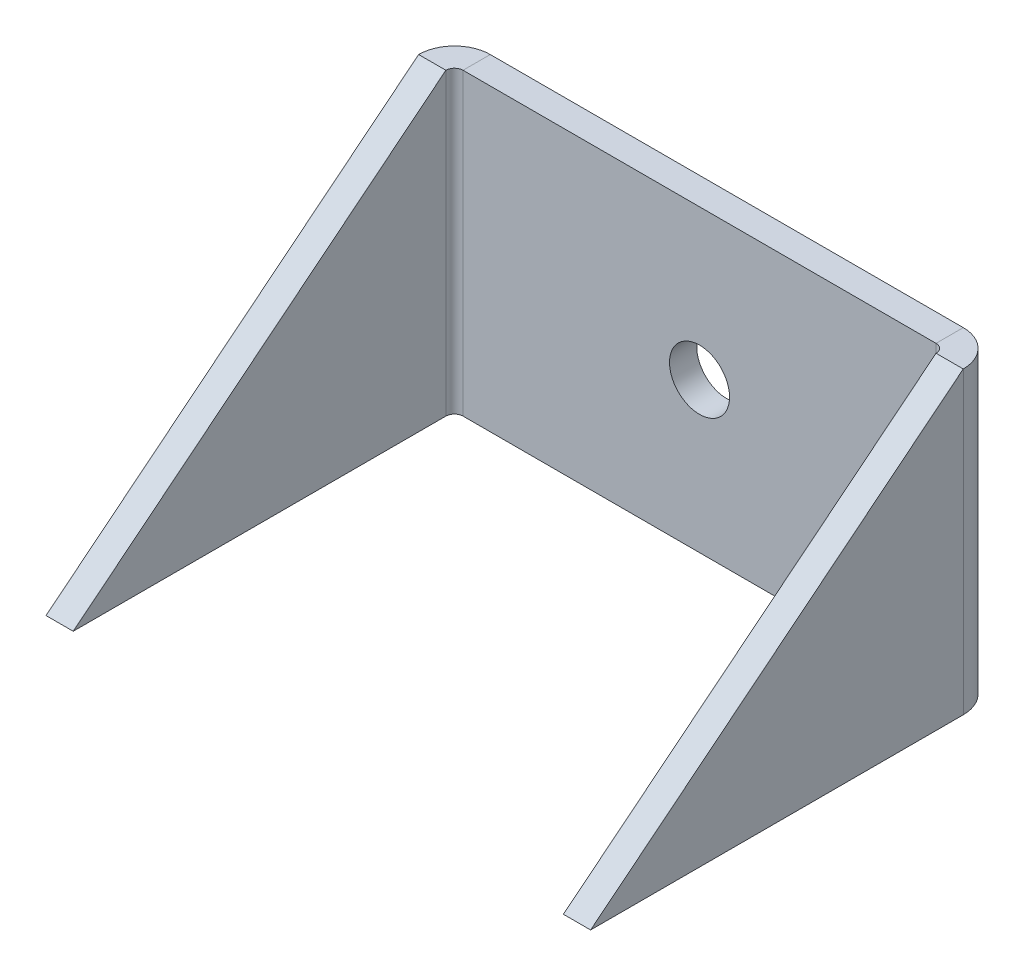
SolidWorks part; units mm, degrees
note: The reader was unsure of these and kept them because the rebuilt part matched: flange length of "Edge-Flange1".
material "6061-T6 (SS)"
ref_plane "X-Y Datum" through (0, 0, 0) normal (0, 0, 1) x (1, 0, 0)
ref_plane "X-Z Datum" through (0, 0, 0) normal (0, 1, 0) x (1, 0, 0)
ref_plane "Y-Z Datum" through (0, 0, 0) normal (1, 0, 0) x (0, 0, -1)
sketch "Sketch2" plane through (0, 0, 0) normal (0, 0, 1) x (1, 0, 0)
  line L1 (-28.575, 17.4625) -> (28.575, 17.4625)
  line L2 (-28.575, 17.4625) -> (-28.575, -17.4625)
  line L3 (-28.575, -17.4625) -> (28.575, -17.4625)
  line L4 (28.575, 17.4625) -> (28.575, -17.4625)
  line L5 (-28.575, 17.4625) -> (28.575, -17.4625) construction
  line L6 (-28.575, -17.4625) -> (28.575, 17.4625) construction
  circle A0 centre (0, 0) radius 3 construction
  point P0 (0, 0)
  dimension "D3" = 6
  dimension "D1" = 34.925
  dimension "D2" = 57.15
base flange "Base-Flange1" sketch "Sketch2" thickness 3.175 reverse thickness direction yes parameters "D1"=1
edge flange "Edge-Flange1" sketch "Sketch9" flange angle 90 flange length 47.625 flange position material outside bend radius 1 thickness 3.175 relief rectangular parameters "D6"=10
sketch "Sketch9" plane through (28.575, 0, 3.175) normal (1, 0, 0) x (0, 1, 0)
  line L2 (-17.4625, 0) -> (-17.4625, 44.45)
  line L3 (-17.4625, 44.45) -> (17.4625, 44.45)
  line L4 (17.4625, 44.45) -> (17.4625, 0)
  line L7 (-17.4625, 0) -> (17.4625, 0) construction
  line L8 (-17.4625, 0) -> (17.4625, 0)
bend "EdgeBend1" bend radius 1 bend angle 90 parameters "D5"=1
sketch "Sketch10" plane through (31.75, 0, 0) normal (1, 0, 0) x (0, 0, -1)
  line L0 (-4.175, 17.4625) -> (-47.625, -17.4625)
  line L1 (-47.625, 17.4625) -> (-47.625, -17.4625) construction
  line L3 (-47.625, -17.4625) -> (-4.175, -17.4625) construction
  line L7 (-4.175, -17.4625) -> (-4.175, 17.4625)
  line L8 (-4.175, 17.4625) -> (-47.625, 17.4625)
  line L9 (-47.625, 17.4625) -> (-47.625, -17.4625)
  line L10 (-47.625, -17.4625) -> (-4.175, -17.4625)
  line L12 (-4.175, 17.4625) -> (-47.625, 17.4625)
  line L13 (-47.625, 17.4625) -> (-47.625, -17.4625)
  dimension "D1" = 0
extrude "Cut-Extrude1" cut sketch "Sketch10" against normal blind 3.175 normal cut yes
mirror "Mirror1" about plane through (0, 0, 0) normal (1, 0, 0) of "Cut-Extrude1", "Edge-Flange1"
bend "MirrorBend1" bend radius 1 bend angle 90 parameters "D5"=2
sketch "Sketch11" [suppressed] plane through (32.75, 0, 0) normal (1, 0, 0) x (0, 0, -1)
  line L0 (-4.175, -15.875) -> (-44.45, 15.875)
extrude "Cut-Extrude2" [suppressed] cut sketch "Sketch11" against normal blind 3.175 and the other way through all
hole_wizard "M6 Clearance Hole1" positions "Sketch13" profile "Sketch14" hole size "M6" standard "ANSI Metric" end condition through all
sketch "Sketch13" plane through (0, 0, 3.175) normal (0, 0, 1) x (1, 0, 0)
  point P0 (0, 0)
sketch "Sketch14" plane through (0, 0, 3.175) normal (1, 0, 0) x (0, -1, 0)
  line L0 (0, 0) -> (0, 3.175)
  line L1 (0, 3.175) -> (3.5, 3.175)
  line L2 (3.5, 3.175) -> (3.5, 0)
  line L5 (3.5, 0) -> (0, 0)
  line L11 (0, -6.35) -> (0, 107.95) construction
  dimension "Thru Hole Dia." = 7
  dimension "Thru Hole Depth" = 3.175
sketch "Bend-Lines1" [suppressed] plane through (0, 0, 0) normal (0, 1, 0) x (1, 0, 0)
sketch "Bounding-Box1" [suppressed] plane through (0, 0, 0) normal (0, 1, 0) x (1, 0, 0)
sheet metal parameters "Sheet-Metal1" thickness 3.175 parameters "D1"=1
flat pattern "Flat-Pattern1" [suppressed]
sketch "Bend-Lines2" plane through (0, 0, 0) normal (0, 1, 0) x (1, 0, 0)
sketch3d "Bounding-Box2" [suppressed]
  line L0 (-63.5, -15.875, 0) -> (63.5, -15.875, 0) construction
  line L1 (-63.5, 15.875, 0) -> (63.5, 15.875, 0) construction
  line L2 (-63.5, -15.875, 0) -> (-63.5, 15.875, 0) construction
  line L3 (63.5, -15.875, 0) -> (63.5, 15.875, 0) construction
sheet metal parameters "Sheet-Metal2" thickness 3.175 parameters "D1"=1
flat pattern "Flat-Pattern1"
sketch "Bend-Lines2" plane through (0, 0, 0) normal (0, 0, -1) x (-1, 0, 0)
  line L0 (-30.6072, 15.875) -> (-30.6072, -15.875) construction
  line L1 (-30.6072, 15.875) -> (-30.6072, -15.875) construction
sketch3d "Bounding-Box2" [suppressed]
  line L0 (28.575, -15.875, 0) -> (-72.9144, -15.875, 0) construction
  line L1 (28.575, 15.875, 0) -> (-72.9144, 15.875, 0) construction
  line L2 (28.575, -15.875, 0) -> (28.575, 15.875, 0) construction
  line L3 (-72.9144, -15.875, 0) -> (-72.9144, 15.875, 0) construction
bend of the flat pattern "Flatten-<EdgeBend1>1"
sheet metal parameters "Sheet-Metal5" thickness 3.175 parameters "D1"=1
flat pattern "Flat-Pattern1"
sketch "Bend-Lines2" plane through (0, 0, 0) normal (0, 0, -1) x (-1, 0, 0)
  line L0 (-29.6072, 15.875) -> (-29.6072, -15.875) construction
  line L1 (-29.6072, 15.875) -> (-29.6072, -15.875) construction
  line L2 (29.6072, -15.875) -> (29.6072, 15.875) construction
  line L3 (29.6072, -15.875) -> (29.6072, 15.875) construction
sketch3d "Bounding-Box2" [suppressed]
  line L0 (71.9144, -15.875, 0) -> (-71.9144, -15.875, 0) construction
  line L1 (71.9144, 15.875, 0) -> (-71.9144, 15.875, 0) construction
  line L2 (71.9144, -15.875, 0) -> (71.9144, 15.875, 0) construction
  line L3 (-71.9144, -15.875, 0) -> (-71.9144, 15.875, 0) construction
bend of the flat pattern "Flatten-<EdgeBend1>1"
bend of the flat pattern "Flatten-<MirrorBend1>1"
sheet metal parameters "Sheet-Metal7" thickness 3.175 parameters "D1"=1
flat pattern "Flat-Pattern1"
sketch "Bend-Lines2" plane through (0, 0, 0) normal (0, 0, -1) x (-1, 0, 0)
  line L0 (-30.6072, 15.875) -> (-30.6072, -15.875) construction
  line L1 (-30.6072, 15.875) -> (-30.6072, -15.875) construction
sketch3d "Bounding-Box2" [suppressed]
  line L0 (28.575, -15.875, 0) -> (-72.9144, -15.875, 0) construction
  line L1 (28.575, 15.875, 0) -> (-72.9144, 15.875, 0) construction
  line L2 (28.575, -15.875, 0) -> (28.575, 15.875, 0) construction
  line L3 (-72.9144, -15.875, 0) -> (-72.9144, 15.875, 0) construction
bend of the flat pattern "Flatten-<EdgeBend1>1"
sheet metal parameters "Sheet-Metal8" thickness 3.175 parameters "D1"=1
flat pattern "Flat-Pattern1"
sketch "Bend-Lines2" plane through (0, 0, 0) normal (0, 0, -1) x (-1, 0, 0)
  line L0 (-30.6072, 15.875) -> (-30.6072, -15.875) construction
  line L1 (-30.6072, 15.875) -> (-30.6072, -15.875) construction
sketch3d "Bounding-Box2" [suppressed]
  line L0 (28.575, -15.875, 0) -> (-72.9144, -15.875, 0) construction
  line L1 (28.575, 15.875, 0) -> (-72.9144, 15.875, 0) construction
  line L2 (28.575, -15.875, 0) -> (28.575, 15.875, 0) construction
  line L3 (-72.9144, -15.875, 0) -> (-72.9144, 15.875, 0) construction
bend of the flat pattern "Flatten-<EdgeBend1>1"
sheet metal parameters "Sheet-Metal9" thickness 3.175 parameters "D1"=1
flat pattern "Flat-Pattern1"
sketch "Bend-Lines2" plane through (0, 0, 0) normal (0, 0, -1) x (-1, 0, 0)
  line L0 (-29.6072, 17.4625) -> (-29.6072, -17.4625) construction
  line L1 (-29.6072, 17.4625) -> (-29.6072, -17.4625) construction
  line L2 (29.6072, -17.4625) -> (29.6072, 17.4625) construction
  line L3 (29.6072, -17.4625) -> (29.6072, 17.4625) construction
sketch3d "Bounding-Box2" [suppressed]
  line L0 (75.0894, -17.4625, 0) -> (-75.0894, -17.4625, 0) construction
  line L1 (75.0894, 17.4625, 0) -> (-75.0894, 17.4625, 0) construction
  line L2 (75.0894, -17.4625, 0) -> (75.0894, 17.4625, 0) construction
  line L3 (-75.0894, -17.4625, 0) -> (-75.0894, 17.4625, 0) construction
bend of the flat pattern "Flatten-<EdgeBend1>1"
bend of the flat pattern "Flatten-<MirrorBend1>1"
